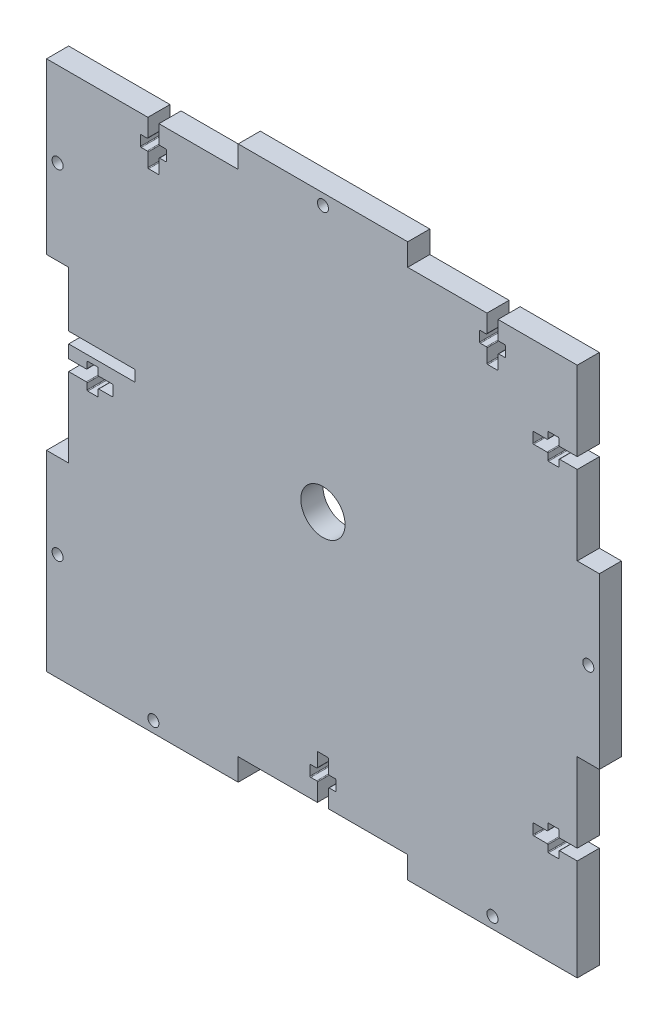
SolidWorks part; units mm, degrees
ref_plane "Front Plane" through (0, 0, 0) normal (0, 0, 1) x (1, 0, 0)
ref_plane "Top Plane" through (0, 0, 0) normal (0, 1, 0) x (1, 0, 0)
ref_plane "Right Plane" through (0, 0, 0) normal (1, 0, 0) x (0, 0, -1)
sketch "Sketch1" plane through (0, 0, 0) normal (0, 0, 1) x (1, 0, 0)
  line L0 (-69, 69) -> (-23, 69)
  line L5 (-75, -75) -> (75, -75) construction
  line L6 (-75, -75) -> (-75, 75) construction
  line L7 (-75, 75) -> (75, 75) construction
  line L8 (75, -75) -> (75, 75) construction
  line L9 (75, 23) -> (69, 23)
  line L10 (69, -23) -> (75, -23)
  line L11 (-69, -69) -> (69, -69) construction
  line L12 (-69, -69) -> (-69, 69) construction
  line L13 (-69, 69) -> (69, 69) construction
  line L14 (69, -69) -> (69, 69) construction
  line L15 (-69, -69) -> (69, 69) construction
  line L16 (69, -69) -> (69, -23)
  line L17 (-23, 69) -> (-23, 75)
  line L18 (-23, 75) -> (23, 75)
  line L19 (23, 75) -> (23, 69)
  line L20 (23, 69) -> (69, 69)
  line L21 (75, -23) -> (75, 23)
  line L22 (69, 23) -> (69, 69)
  line L23 (-75, 23) -> (-69, 23)
  line L24 (-69, 69) -> (-75, 69)
  line L25 (-75, 69) -> (-75, 23)
  line L26 (69, -69) -> (69, -75)
  line L27 (69, -75) -> (23, -75)
  line L28 (23, -75) -> (23, -69)
  line L29 (23, -69) -> (-23, -69)
  line L30 (-23, -69) -> (-23, -75)
  line L31 (-23, -75) -> (-69, -75)
  line L32 (-69, -75) -> (-69, -69) construction
  line L33 (-69, 23) -> (-69, -23)
  line L34 (-69, -23) -> (-75, -23)
  line L35 (-75, -23) -> (-75, -69)
  line L36 (-75, -69) -> (-69, -69) construction
  line L37 (-46, 69) -> (-46, -75) construction
  line L38 (-69, 69) -> (69, -69) construction
  line L39 (-75, -75) -> (-69, -75)
  line L40 (-75, -75) -> (-75, -69)
  point P0 (0, 0)
  point P6 (-7, -7)
  point P26 (0, -75)
  point P27 (-75, 0)
  dimension "D1" = 150
  dimension "D2" = 150
  dimension "D5" = 46
  dimension "D3" = 6
  dimension "D6" = 6
  dimension "D7" = 6
extrude "Box Side" add sketch "Sketch1" along normal blind 6
sketch "Sketch2" plane through (0, 0, 6) normal (0, 0, 1) x (1, 0, 0)
  line L0 (23, 72) -> (-23, 72) construction
  line L1 (23, 75) -> (23, 69) construction
  line L2 (-23, 69) -> (-23, 75) construction
  line L3 (-46, 69) -> (-46, -75) construction
  line L5 (0, 75) -> (0, 69) construction
  line L6 (-23, 75) -> (23, 75) construction
  line L7 (-69, 69) -> (69, 69) construction
  line L16 (-46, 69) -> (-46, -75) construction
  line L21 (0, -69) -> (0, 69) construction
  line L35 (-69, 69) -> (-23, 69) construction
  line L36 (-44.5, 69) -> (-44.5, 64.2)
  line L37 (-44.3, 64) -> (-42.7, 64)
  line L38 (-42.5, 63.8) -> (-42.5, 61.2)
  line L39 (-42.7, 61) -> (-44.3, 61)
  line L40 (-44.5, 60.8) -> (-44.5, 57.2)
  line L46 (-44.7, 57) -> (-47.3, 57)
  line L48 (-44.5, 69) -> (-47.5, 69)
  line L51 (-47.5, 60.8) -> (-47.5, 57.2)
  line L52 (-49.3, 61) -> (-47.7, 61)
  line L53 (-49.5, 63.8) -> (-49.5, 61.2)
  line L54 (-47.7, 64) -> (-49.3, 64)
  line L55 (-47.5, 69) -> (-47.5, 64.2)
  line L56 (47.5, 69) -> (47.5, 64.2)
  line L57 (47.7, 64) -> (49.3, 64)
  line L58 (49.5, 63.8) -> (49.5, 61.2)
  line L59 (49.3, 61) -> (47.7, 61)
  line L60 (47.5, 60.8) -> (47.5, 57.2)
  line L61 (44.5, 69) -> (47.5, 69)
  line L62 (44.7, 57) -> (47.3, 57)
  line L63 (44.5, 60.8) -> (44.5, 57.2)
  line L64 (42.7, 61) -> (44.3, 61)
  line L65 (42.5, 63.8) -> (42.5, 61.2)
  line L66 (44.3, 64) -> (42.7, 64)
  line L67 (44.5, 69) -> (44.5, 64.2)
  line L68 (-69, -69) -> (69, 69) construction
  line L69 (-69, -69) -> (69, 69) construction
  line L70 (75, 0) -> (69, 0) construction
  line L71 (72, 23) -> (72, -23) construction
  line L72 (69, 44.5) -> (64.2, 44.5)
  line L73 (64, 44.3) -> (64, 42.7)
  line L74 (63.8, 42.5) -> (61.2, 42.5)
  line L75 (61, 42.7) -> (61, 44.3)
  line L76 (60.8, 44.5) -> (57.2, 44.5)
  line L77 (57, 44.7) -> (57, 47.3)
  line L78 (69, 44.5) -> (69, 47.5)
  line L79 (60.8, 47.5) -> (57.2, 47.5)
  line L80 (61, 49.3) -> (61, 47.7)
  line L81 (63.8, 49.5) -> (61.2, 49.5)
  line L82 (64, 47.7) -> (64, 49.3)
  line L83 (69, 47.5) -> (64.2, 47.5)
  line L84 (69, -47.5) -> (64.2, -47.5)
  line L85 (64, -47.7) -> (64, -49.3)
  line L86 (63.8, -49.5) -> (61.2, -49.5)
  line L87 (61, -49.3) -> (61, -47.7)
  line L88 (60.8, -47.5) -> (57.2, -47.5)
  line L89 (69, -44.5) -> (69, -47.5)
  line L90 (57, -44.7) -> (57, -47.3)
  line L91 (60.8, -44.5) -> (57.2, -44.5)
  line L92 (61, -42.7) -> (61, -44.3)
  line L93 (63.8, -42.5) -> (61.2, -42.5)
  line L94 (64, -44.3) -> (64, -42.7)
  line L95 (69, -44.5) -> (64.2, -44.5)
  line L120 (-69, 69) -> (69, -69) construction
  line L121 (-69, 69) -> (69, -69) construction
  line L122 (-1.5, -69) -> (1.5, -69)
  line L123 (-23, -69) -> (23, -69) construction
  line L124 (1.5, -69) -> (1.5, -64.2)
  line L125 (1.7, -64) -> (3.3, -64)
  line L126 (3.5, -63.8) -> (3.5, -61.2)
  line L127 (3.3, -61) -> (1.7, -61)
  line L128 (1.5, -60.8) -> (1.5, -57.2)
  line L129 (1.3, -57) -> (-1.3, -57)
  line L130 (-1.5, -60.8) -> (-1.5, -57.2)
  line L131 (-3.3, -61) -> (-1.7, -61)
  line L132 (-3.5, -63.8) -> (-3.5, -61.2)
  line L133 (-1.7, -64) -> (-3.3, -64)
  line L134 (-1.5, -69) -> (-1.5, -64.2)
  line L135 (-69, -1.5) -> (-64.2, -1.5)
  line L136 (-64, -1.7) -> (-64, -3.3)
  line L137 (-63.8, -3.5) -> (-61.2, -3.5)
  line L138 (-61, -3.3) -> (-61, -1.7)
  line L139 (-60.8, -1.5) -> (-57.2, -1.5)
  line L140 (-57, 1.3) -> (-57, -1.3)
  line L141 (-60.8, 1.5) -> (-57.2, 1.5)
  line L142 (-61, 3.3) -> (-61, 1.7)
  line L143 (-63.8, 3.5) -> (-61.2, 3.5)
  line L144 (-64, 1.7) -> (-64, 3.3)
  line L145 (-69, 1.5) -> (-64.2, 1.5)
  line L146 (-69, -1.5) -> (-69, 1.5)
  line L147 (-69, -72) -> (-23, -72) construction
  line L148 (-23, 69) -> (-75, 69) construction
  line L149 (-23, -75) -> (-23, -69) construction
  line L150 (-69, -69) -> (-69, -75) construction
  line L151 (-75, -75) -> (-23, -75) construction
  circle A0 centre (0, 72) radius 1.5
  arc A1 (-44.5, 57.2) -> (-44.7, 57) centre (-44.7, 57.2) cw
  arc A2 (-44.3, 61) -> (-44.5, 60.8) centre (-44.3, 60.8) ccw
  arc A3 (-42.5, 61.2) -> (-42.7, 61) centre (-42.7, 61.2) cw
  arc A4 (-42.7, 64) -> (-42.5, 63.8) centre (-42.7, 63.8) cw
  arc A5 (-44.5, 64.2) -> (-44.3, 64) centre (-44.3, 64.2) ccw
  arc A6 (-47.5, 64.2) -> (-47.7, 64) centre (-47.7, 64.2) cw
  arc A7 (-49.3, 64) -> (-49.5, 63.8) centre (-49.3, 63.8) ccw
  arc A8 (-49.5, 61.2) -> (-49.3, 61) centre (-49.3, 61.2) ccw
  arc A9 (-47.7, 61) -> (-47.5, 60.8) centre (-47.7, 60.8) cw
  arc A10 (-47.5, 57.2) -> (-47.3, 57) centre (-47.3, 57.2) ccw
  arc A11 (47.5, 57.2) -> (47.3, 57) centre (47.3, 57.2) cw
  arc A12 (47.7, 61) -> (47.5, 60.8) centre (47.7, 60.8) ccw
  arc A13 (49.5, 61.2) -> (49.3, 61) centre (49.3, 61.2) cw
  arc A14 (49.3, 64) -> (49.5, 63.8) centre (49.3, 63.8) cw
  arc A15 (47.5, 64.2) -> (47.7, 64) centre (47.7, 64.2) ccw
  arc A16 (44.5, 64.2) -> (44.3, 64) centre (44.3, 64.2) cw
  arc A17 (42.7, 64) -> (42.5, 63.8) centre (42.7, 63.8) ccw
  arc A18 (42.5, 61.2) -> (42.7, 61) centre (42.7, 61.2) ccw
  arc A19 (44.3, 61) -> (44.5, 60.8) centre (44.3, 60.8) cw
  arc A20 (44.5, 57.2) -> (44.7, 57) centre (44.7, 57.2) ccw
  arc A21 (57.2, 44.5) -> (57, 44.7) centre (57.2, 44.7) cw
  arc A22 (61, 44.3) -> (60.8, 44.5) centre (60.8, 44.3) ccw
  arc A23 (61.2, 42.5) -> (61, 42.7) centre (61.2, 42.7) cw
  arc A24 (64, 42.7) -> (63.8, 42.5) centre (63.8, 42.7) cw
  arc A25 (64.2, 44.5) -> (64, 44.3) centre (64.2, 44.3) ccw
  arc A26 (64.2, 47.5) -> (64, 47.7) centre (64.2, 47.7) cw
  arc A27 (64, 49.3) -> (63.8, 49.5) centre (63.8, 49.3) ccw
  arc A28 (61.2, 49.5) -> (61, 49.3) centre (61.2, 49.3) ccw
  arc A29 (61, 47.7) -> (60.8, 47.5) centre (60.8, 47.7) cw
  arc A30 (57.2, 47.5) -> (57, 47.3) centre (57.2, 47.3) ccw
  arc A31 (57.2, -47.5) -> (57, -47.3) centre (57.2, -47.3) cw
  arc A32 (61, -47.7) -> (60.8, -47.5) centre (60.8, -47.7) ccw
  arc A33 (61.2, -49.5) -> (61, -49.3) centre (61.2, -49.3) cw
  arc A34 (64, -49.3) -> (63.8, -49.5) centre (63.8, -49.3) cw
  arc A35 (64.2, -47.5) -> (64, -47.7) centre (64.2, -47.7) ccw
  arc A36 (64.2, -44.5) -> (64, -44.3) centre (64.2, -44.3) cw
  arc A37 (64, -42.7) -> (63.8, -42.5) centre (63.8, -42.7) ccw
  arc A38 (61.2, -42.5) -> (61, -42.7) centre (61.2, -42.7) ccw
  arc A39 (61, -44.3) -> (60.8, -44.5) centre (60.8, -44.3) cw
  arc A40 (57.2, -44.5) -> (57, -44.7) centre (57.2, -44.7) ccw
  circle A41 centre (72, 0) radius 1.5
  arc A62 (1.5, -57.2) -> (1.3, -57) centre (1.3, -57.2) ccw
  arc A63 (1.7, -61) -> (1.5, -60.8) centre (1.7, -60.8) cw
  arc A64 (3.5, -61.2) -> (3.3, -61) centre (3.3, -61.2) ccw
  arc A65 (3.3, -64) -> (3.5, -63.8) centre (3.3, -63.8) ccw
  arc A66 (1.5, -64.2) -> (1.7, -64) centre (1.7, -64.2) cw
  arc A67 (-1.5, -64.2) -> (-1.7, -64) centre (-1.7, -64.2) ccw
  arc A68 (-3.3, -64) -> (-3.5, -63.8) centre (-3.3, -63.8) cw
  arc A69 (-3.5, -61.2) -> (-3.3, -61) centre (-3.3, -61.2) cw
  arc A70 (-1.7, -61) -> (-1.5, -60.8) centre (-1.7, -60.8) ccw
  arc A71 (-1.5, -57.2) -> (-1.3, -57) centre (-1.3, -57.2) cw
  arc A72 (-57.2, -1.5) -> (-57, -1.3) centre (-57.2, -1.3) ccw
  arc A73 (-61, -1.7) -> (-60.8, -1.5) centre (-60.8, -1.7) cw
  arc A74 (-61.2, -3.5) -> (-61, -3.3) centre (-61.2, -3.3) ccw
  arc A75 (-64, -3.3) -> (-63.8, -3.5) centre (-63.8, -3.3) ccw
  arc A76 (-64.2, -1.5) -> (-64, -1.7) centre (-64.2, -1.7) cw
  arc A77 (-64.2, 1.5) -> (-64, 1.7) centre (-64.2, 1.7) ccw
  arc A78 (-64, 3.3) -> (-63.8, 3.5) centre (-63.8, 3.3) cw
  arc A79 (-61.2, 3.5) -> (-61, 3.3) centre (-61.2, 3.3) cw
  arc A80 (-61, 1.7) -> (-60.8, 1.5) centre (-60.8, 1.7) ccw
  arc A81 (-57.2, 1.5) -> (-57, 1.3) centre (-57.2, 1.3) cw
  circle A82 centre (-46, -72) radius 1.5
  circle A83 centre (46, -72) radius 1.5
  circle A84 centre (-72, 46) radius 1.5
  circle A85 centre (-72, -46) radius 1.5
  point P6 (0, 72)
  point P38 (0, 0)
  point P56 (-46, 57)
  point P88 (46, 57)
  point P161 (57, 46)
  point P162 (57, -46)
  point P198 (0, -57)
  point P231 (-57, 0)
  point P234 (-42.5, 62.5)
  dimension "D1" = 3
  dimension "D2" = 0.2
  dimension "D8" = 0.2
  dimension "D14" = 3
  dimension "D4" = 3
  dimension "D7" = 1.5
  dimension "D10" = 3
  dimension "D12" = 1.5
  dimension "D9" = 12
  dimension "D11" = 5
  dimension "D13" = 7
  dimension "D3" = 12
  dimension "D5" = 7
  dimension "D6" = 5
extrude "Screw Cut-outs" cut sketch "Sketch2" against normal through all
sketch "Sketch3" plane through (0, 0, 6) normal (0, 0, 1) x (1, 0, 0)
  line L0 (-69, -69) -> (69, 69) construction
  line L1 (-69, -69) -> (69, 69) construction
  line L2 (-69, 69) -> (69, -69) construction
  line L3 (-69, 69) -> (69, -69) construction
  circle A0 centre (0, 0) radius 6
  point P4 (0, 0)
  dimension "D1" = 12
extrude "BearingHole" cut sketch "Sketch3" against normal through all
sketch "Sketch4" plane through (0, 0, 6) normal (0, 0, 1) x (1, 0, 0)
  line L0 (-69, 23) -> (-69, 1.5) construction
  line L1 (-69, 5) -> (-51, 5)
  line L2 (-69, 5) -> (-69, 8)
  line L3 (-69, 8) -> (-51, 8)
  line L4 (-51, 5) -> (-51, 8)
  line L5 (-61.2, 3.5) -> (-63.8, 3.5) construction
  dimension "D1" = 3
  dimension "D2" = 1.5
  dimension "D3" = 18
extrude "Cut-Extrude1" cut sketch "Sketch4" against normal up to surface (6 mm away) up to face at (6, 0, 0)
equation "\"filletRadius\"=0.2"
equation "\"D8@Sketch2\"=\"filletRadius\""
equation "\"D2@Sketch2\"=\"filletRadius\""
equation "\"fingerWidth\"= 46"
equation "\"D5@Sketch1\"=\"fingerWidth\""
equation "\"wallThickness\"= 6"
equation "\"D3@Sketch1\" = \"wallThickness\""
equation "\"D6@Sketch1\" = \"wallThickness\""
equation "\"D7@Sketch1\" = \"wallThickness\""
equation "\"D1@Box Side\" = \"wallThickness\""
equation "\"M3\"= 3"
equation "\"D14@Sketch2\"=\"M3\""
equation "\"D1@Sketch2\"=\"M3\""
equation "\"D12@Sketch2\"=\"M3\"/2"
equation "\"nutThickness\"=3"
equation "\"D10@Sketch2\" = \"nutThickness\""
equation "\"boltLength\"= 12"
equation "\"D9@Sketch2\" = \"boltLength\""
equation "\"distanceToNut\"= 5"
equation "\"D11@Sketch2\" = \"distanceToNut\""
equation "\"D13@Sketch2\" = \"nutWidth\""
equation "\"D7@Sketch2\"=\"M3\"/2"
equation "\"D4@Sketch2\" = \"nutThickness\""
equation "\"D3@Sketch2\" = \"boltLength\""
equation "\"D5@Sketch2\" = \"nutWidth\""
equation "\"D6@Sketch2\" = \"distanceToNut\""
equation "\"sideLength\"=150"
equation "\"D1@Sketch1\"=\"sideLength\""
equation "\"D2@Sketch1\"=\"sideLength\""
equation "\"nutWidth\"=7"
